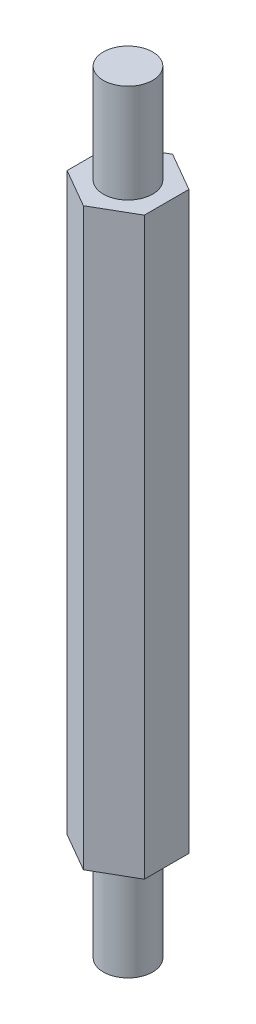
SolidWorks part; units mm, degrees
ref_plane "Front Plane" through (0, 0, 0) normal (0, 0, 1) x (1, 0, 0)
ref_plane "Top Plane" through (0, 0, 0) normal (0, 1, 0) x (1, 0, 0)
ref_plane "Right Plane" through (0, 0, 0) normal (1, 0, 0) x (0, 0, -1)
sketch "Sketch1" plane through (0, 0, 0) normal (0, 1, 0) x (1, 0, 0)
  line L1 (0, 2.7135) -> (-2.35, 1.3568)
  line L2 (-2.35, 1.3568) -> (-2.35, -1.3568)
  line L3 (-2.35, -1.3568) -> (0, -2.7135)
  line L4 (0, -2.7135) -> (2.35, -1.3568)
  line L5 (2.35, -1.3568) -> (2.35, 1.3568)
  line L6 (2.35, 1.3568) -> (0, 2.7135)
  circle A0 centre (0, 0) radius 2.35 construction
  dimension "D1" = 4.7
extrude "Boss-Extrude1" add sketch "Sketch1" along normal blind 35
sketch "Sketch2" plane through (0, 35, 0) normal (0, 1, 0) x (1, 0, 0)
  circle A0 centre (0, 0) radius 1.5
  dimension "D1" = 3
extrude "Boss-Extrude2" add sketch "Sketch2" along normal blind 6
sketch "Sketch5" plane through (0, 0, 0) normal (0, -1, 0) x (1, 0, 0)
  circle A0 centre (0, 0) radius 1.5
  dimension "D1" = 3
extrude "Boss-Extrude3" add sketch "Sketch5" along normal blind 6 contours A0
